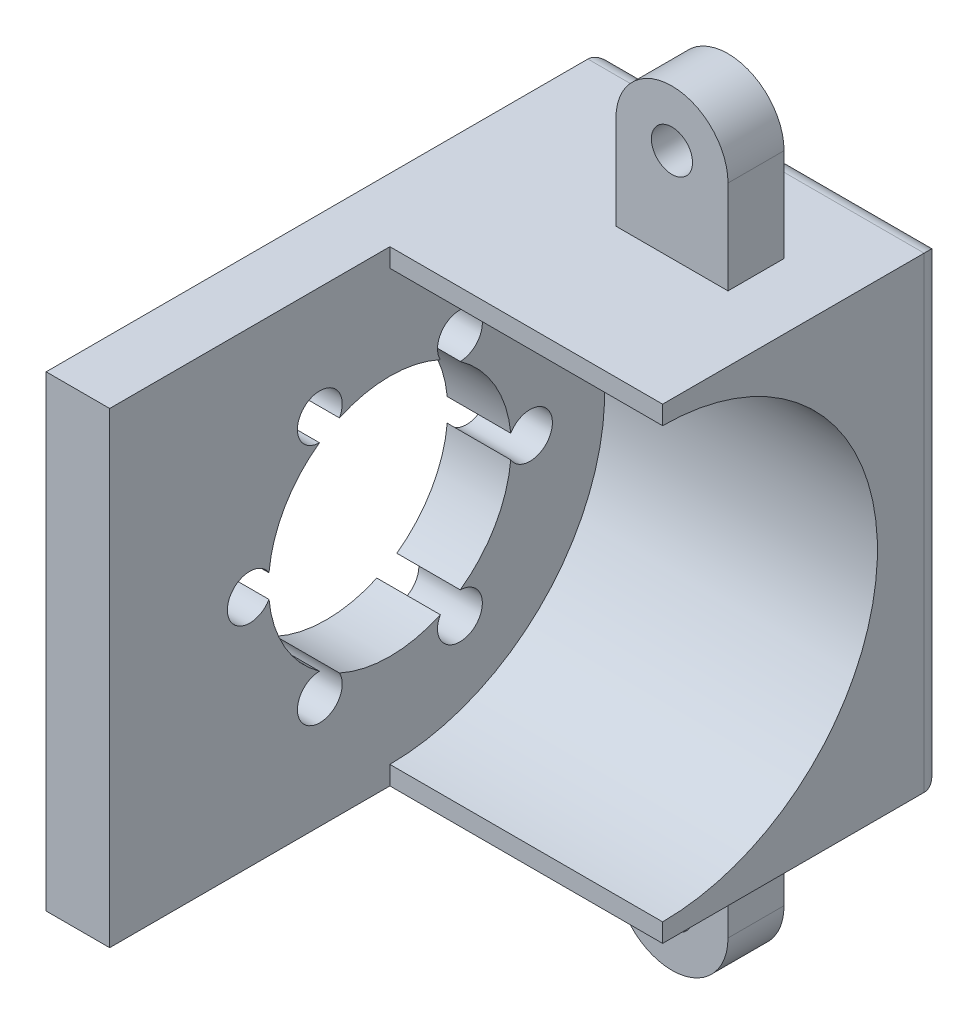
SolidWorks part; units mm, degrees
ref_plane "前视基准面" through (0, 0, 0) normal (0, 0, 1) x (1, 0, 0)
ref_plane "上视基准面" through (0, 0, 0) normal (0, 1, 0) x (1, 0, 0)
ref_plane "右视基准面" through (0, 0, 0) normal (1, 0, 0) x (0, 0, -1)
sketch "草图1" plane through (0, 0, 0) normal (0, 0, 1) x (1, 0, 0)
  line L9 (-11.5, 12.5) -> (11.5, 12.5)
  line L10 (-11.5, 12.5) -> (-11.5, -12.5)
  line L11 (-11.5, -12.5) -> (11.5, -12.5)
  line L12 (11.5, 12.5) -> (11.5, -12.5)
  line L13 (0, -12.5) -> (0, 12.5) construction
  line L14 (-11.5, 0) -> (11.5, 0) construction
  point P0 (0, 0)
  dimension "D1" = 23
  dimension "D2" = 25
extrude "凸台-拉伸1" add sketch "草图1" against normal blind 15 contours L12 L9 L10 L11 region at (0, 0, 0)
ref_axis "基准轴2" through (11.5, 0, 0) along (-1, 0, 0)
sketch "草图2" plane through (0, 0, 0) normal (0, 0, 1) x (1, 0, 0)
  line L0 (11.5, 0) -> (-11.5, 0) construction
  line L1 (11.5, 12.5) -> (11.5, -12.5) construction
  line L2 (11.5, 12.5) -> (11.5, -12.5) construction
  line L3 (11.5, 0) -> (11.5, -11.5)
  line L4 (11.5, -11.5) -> (-8.1, -11.5)
  line L9 (-8.1, -11.5) -> (-8.1, 0)
  line L10 (11.5, 0) -> (-8.1, 0)
  dimension "D1" = 11.5
  dimension "D2" = 19.6
revolve "切除-旋转2" cut sketch "草图2" angle 360 about axis through (11.5, 0, 0) along (-1, 0, 0)
ref_plane "基准面1" through (0, 0, 0) normal (0, 0, 1) x (1, 0, 0)
sketch "草图4" plane through (0, 0, 0) normal (0, 0, 1) x (1, 0, 0)
  line L0 (-8.1, 12.5) -> (-8.1, -12.5)
  line L1 (-11.5, 12.5) -> (11.5, 12.5) construction
  line L2 (-8.1, -12.5) -> (-11.5, -12.5)
  line L3 (-11.5, -12.5) -> (-11.5, 12.5)
  line L4 (-11.5, 12.5) -> (-8.1, 12.5)
  line L5 (-8.1, -11.5) -> (-8.1, 11.5) construction
  line L6 (-8.1, -11.5) -> (-8.1, 10.9) construction
  dimension "D1" = 25
extrude "凸台-拉伸2" add sketch "草图4" along normal blind 15
ref_plane "基准面2" through (-8.1, 0, 0) normal (1, 0, 0) x (0, 0, -1)
sketch "草图6" plane through (-8.1, 0, 0) normal (1, 0, 0) x (0, 0, -1)
  line L0 (0, 0) -> (7.5, 0) construction
  circle A0 centre (0, 0) radius 7.5 construction
  circle A1 centre (7.5, 0) radius 1.2
  circle A2 centre (3.75, -6.4952) radius 1.2
  circle A3 centre (-3.75, -6.4952) radius 1.2
  circle A5 centre (0, 0) radius 6.5
  circle A6 centre (-7.5, 0) radius 1.2
  circle A7 centre (-3.75, 6.4952) radius 1.2
  circle A8 centre (3.75, 6.4952) radius 1.2
  point P12 (0, 0)
  dimension "D1" = 15
  dimension "D2" = 2.4
  dimension "D5" = 13
  dimension "D3" = 6
extrude "切除-拉伸1" cut sketch "草图6" against normal blind 4 contours A7 | A6 | A8 | A1 | A3 | A2 | A5 region at (-8.1, 0, -7.5415) region at (-8.1, 6.5312, -3.7708) region at (-8.1, -6.5312, -3.7708) region at (-8.1, 6.5312, 3.7708) region at (-8.1, -6.5312, 3.7708) region at (-8.1, 0, 7.5415)
sketch "草图8" plane through (0, 0, -15) normal (0, 0, -1) x (-1, 0, 0)
  line L0 (11.5, -12.5) -> (-11.5, -12.5) construction
  line L1 (0, -1026.5) -> (0, -20.5) construction
  line L2 (11.5, 0) -> (2.7493, 0) construction
  line L3 (3, 17.5) -> (3, 12.5)
  line L5 (-3, -17.5) -> (-3, -12.5)
  line L6 (-3, -12.5) -> (3, -12.5)
  line L7 (3, -17.5) -> (3, -12.5)
  line L8 (-3, 17.5) -> (-3, 12.5)
  line L9 (-3, -15) -> (3, -15) construction
  line L10 (0, -12.5) -> (0, 0) construction
  line L11 (-3, 12.5) -> (3, 12.5)
  line L19 (11.5, 0) -> (16.5, 0) construction
  arc A0 (-3, -17.5) -> (3, -17.5) centre (0, -17.5) ccw
  circle A1 centre (0, -17.5) radius 1.1
  arc A2 (-3, 17.5) -> (3, 17.5) centre (0, 17.5) cw
  circle A3 centre (0, 17.5) radius 1.1
  point P5 (0, -15)
  point P28 (0, -12.5)
  dimension "D3" = 3
  dimension "D4" = 2.2
  dimension "D1" = 5
  dimension "D2" = 6
extrude "凸台-拉伸3" add sketch "草图8" against normal blind 8
extrude "切除-拉伸4" cut sketch "草图8<2>" against normal blind 5
sketch "草图8<2>" plane through (0, 0, -15) normal (0, 0, -1) x (-1, 0, 0) same geometry as "草图8"
sketch "草图7" plane through (11.5, 0, 0) normal (1, 0, 0) x (0, 0, -1)
  line L1 (-6, -20) -> (29, -20)
  line L2 (-6, -20) -> (-6, 20)
  line L3 (-6, 20) -> (29, 20)
  line L4 (29, -20) -> (29, 20)
  line L5 (11.5, 20) -> (11.5, -20) construction
  line L6 (-6, 0) -> (29, 0) construction
  arc A0 (0, -11.5) -> (0, 11.5) centre (0, 0) ccw construction
  point P4 (11.5, 0)
  dimension "D1" = 40
  dimension "D2" = 35
extrude "切除-拉伸3" cut sketch "草图7" against normal blind 5
fillet "圆角1" radius 1 4 edges at (-2.5, -12.5, -15) (-11.5, 0, -15) (-2.5, 12.5, -15) (6.5, 0, -15)
